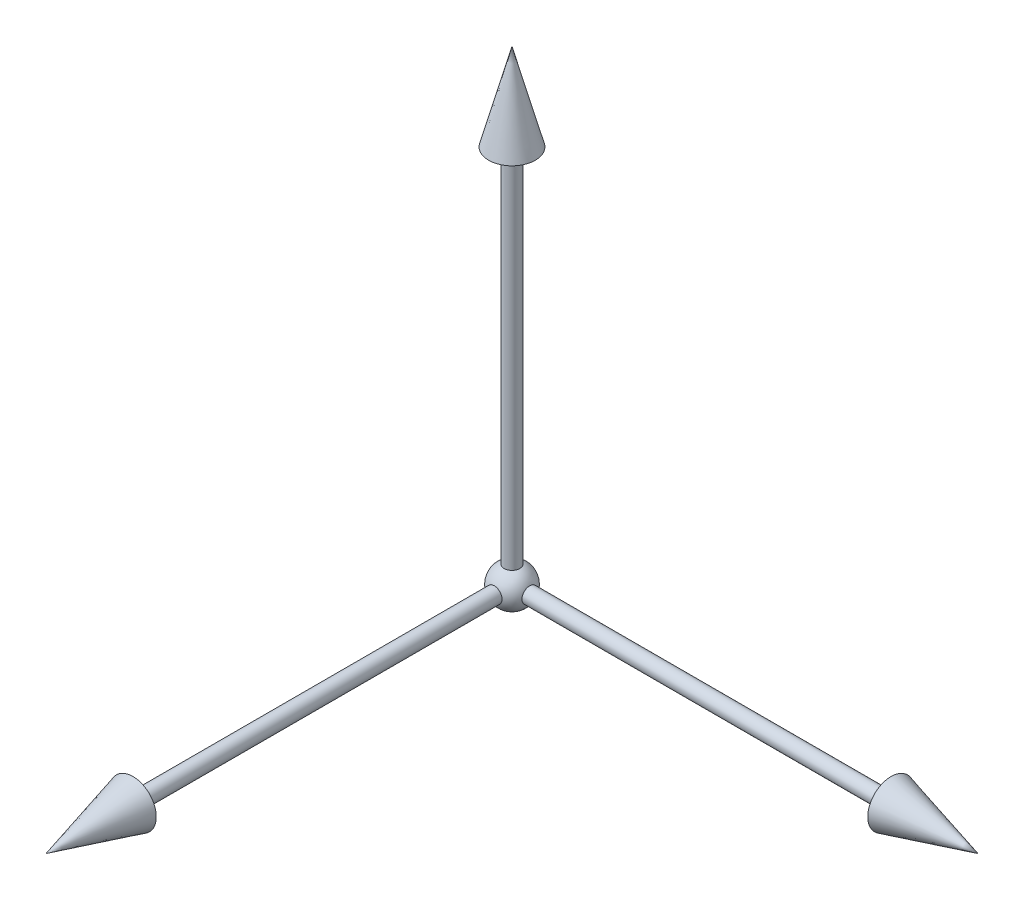
SolidWorks part; units mm, degrees
note: '?' marks a value the reader was unsure of.
ref_plane "Спереди" through (0, 0, 0) normal (0, 0, 1) x (1, 0, 0)
ref_plane "Сверху" through (0, 0, 0) normal (0, 1, 0) x (1, 0, 0)
ref_plane "Справа" through (0, 0, 0) normal (1, 0, 0) x (0, 0, -1)
ref_axis "X" through (-80.9, 0, 0) along (1, 0, 0)?
ref_axis "Z" through (0, 0, -80.9) along (0, 0, 1)?
ref_axis "Y" through (0, 50, 0) along (0, -1, 0)?
other "Заморозка***"
sketch "Эскиз1" plane through (0, 0, 0) normal (0, 0, 1) x (1, 0, 0)
  line L0 (0, 0) -> (0, 58.1708) construction
  line L1 (0, 50) -> (0, -50) construction
  line L2 (-80.9, 0) -> (80.9, 0) construction
  line L4 (0, 30) -> (0, 0)
  line L5 (0, 0) -> (0.5, 0)
  line L6 (0.5, 24.4019) -> (0.5, 0)
  line L7 (0, 30) -> (1.5, 24.4019)
  line L8 (1.5, 24.4019) -> (0.5, 24.4019)
  dimension "D1" = 1
  dimension "D2" = 3
  dimension "D3" = 30
  dimension "D4" = 15
revolve "Повернуть1" add sketch "Эскиз1" angle 360 about L0
pattern_circular "Круговой массив1" count 2 every 90 about axis through (-80.9, 0, 0) along (1, 0, 0) of bodies 103
pattern_circular "Круговой массив2" count 2 every 90 about axis through (0, 0, -80.9) along (0, 0, 1)
sketch "Эскиз2" plane through (0, 0, 0) normal (0, 0, 1) x (1, 0, 0)
  line L0 (0, 1.25) -> (0, -1.25)
  circle A3 centre (0, 0) radius 1.25
  arc A4 (0, -1.25) -> (0, 1.25) centre (0, 0) ccw
  dimension "D1" = 0.75
revolve "Повернуть2" add sketch "Эскиз2" angle 360 about L0
